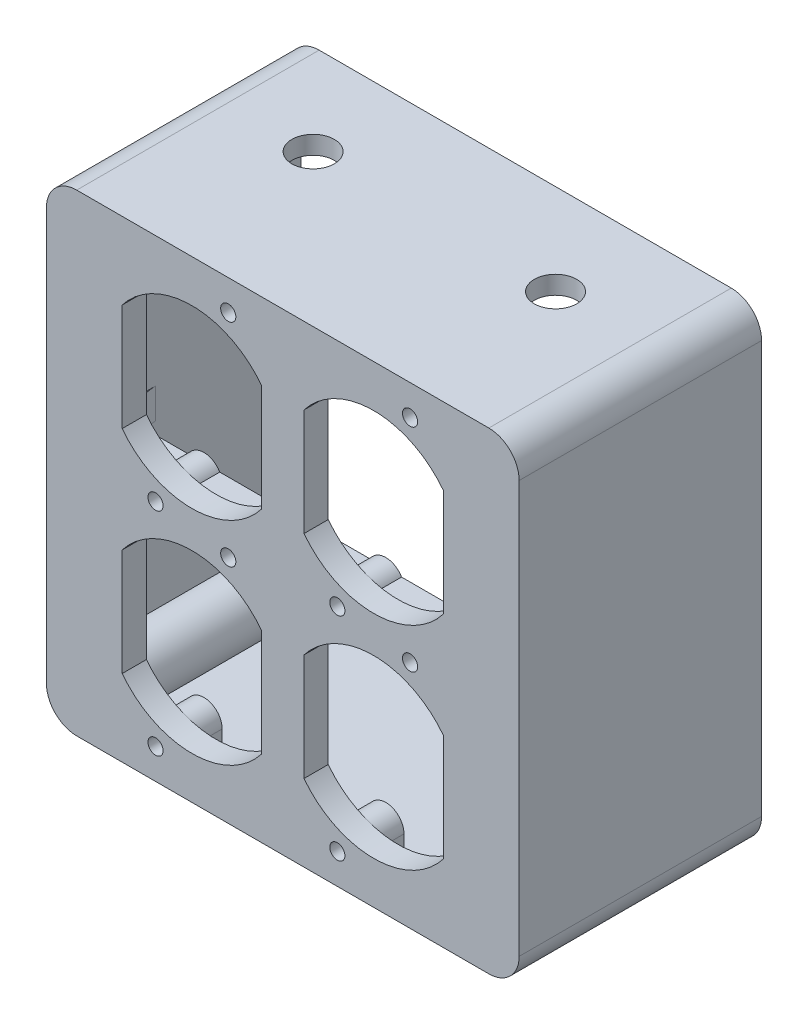
SolidWorks part; units mm, degrees
ref_plane "Front Plane" through (0, 0, 0) normal (0, 0, 1) x (1, 0, 0)
ref_plane "Top Plane" through (0, 0, 0) normal (0, 1, 0) x (1, 0, 0)
ref_plane "Right Plane" through (0, 0, 0) normal (1, 0, 0) x (0, 0, -1)
sketch "Sketch1" plane through (0, 0, 0) normal (0, 0, 1) x (1, 0, 0)
  line L1 (-39, -39) -> (39, -39)
  line L2 (-39, -39) -> (-39, 39)
  line L3 (-39, 39) -> (39, 39)
  line L4 (39, -39) -> (39, 39)
  line L5 (-39, -39) -> (39, 39) construction
  line L6 (-39, 39) -> (39, -39) construction
  point P0 (0, 0)
  dimension "D1" = 78
  dimension "D2" = 78
extrude "Boss-Extrude1" add sketch "Sketch1" along normal blind 40
sketch "Sketch8" plane through (0, 0, 0) normal (0, 0, -1) x (-1, 0, 0)
  line L14 (36, -36) -> (36, 36)
  line L15 (-36, -36) -> (36, -36)
  line L16 (-36, 36) -> (-36, -36)
  line L17 (36, 36) -> (-36, 36)
  line L18 (36, -36) -> (36, 36)
  line L19 (-36, -36) -> (36, -36)
  line L20 (-36, 36) -> (-36, -36)
  line L21 (36, 36) -> (-36, 36)
  dimension "D1" = 3
extrude "Cut-Extrude4" cut sketch "Sketch8" against normal offset from surface (36 mm away) 4 up to face at (0, 0, 40)
sketch "Sketch11" plane through (0, 0, 40) normal (0, 0, 1) x (1, 0, 0)
  line L0 (-39, 39) -> (-39, -39) construction
  line L1 (39, 2.5) -> (-39, 2.5)
  line L2 (39, 2.5) -> (39, -2.5)
  line L3 (39, -2.5) -> (-39, -2.5)
  line L4 (-39, 2.5) -> (-39, -2.5)
  line L5 (39, 2.5) -> (-39, -2.5) construction
  line L6 (39, -2.5) -> (-39, 2.5) construction
  point P0 (0, 0)
  dimension "D1" = 5
extrude "Boss-Extrude4" add sketch "Sketch11" against normal blind 8
sketch "Sketch2" plane through (0, 0, 40) normal (0, 0, 1) x (1, 0, 0)
  line L2 (-26.5, 8.6682) -> (-26.5, 26.3318)
  line L4 (-3.5, 8.6682) -> (-3.5, 26.3318)
  line L5 (-26.5, 8.6682) -> (-3.5, 26.3318) construction
  line L6 (-26.5, 26.3318) -> (-3.5, 8.6682) construction
  arc A0 (-26.5, 26.3318) -> (-3.5, 26.3318) centre (-15, 17.5) cw
  arc A1 (-26.5, 8.6682) -> (-3.5, 8.6682) centre (-15, 17.5) ccw
  point P0 (-15, 17.5)
  point P7 (-15, 3)
  point P9 (-15, 32)
  dimension "D1" = 23
  dimension "D2" = 17.5
  dimension "D3" = 15
  dimension "D4" = 29
extrude "Cut-Extrude1" cut sketch "Sketch2" against normal through all
sketch "Sketch3" plane through (0, 0, 40) normal (0, 0, 1) x (1, 0, 0)
  line L0 (-15, 32) -> (-15, 3) construction
  circle A0 centre (-9, 34) radius 1.25
  circle A1 centre (-21, 1) radius 1.25
  arc A2 (-3.5, 26.3318) -> (-26.5, 26.3318) centre (-15, 17.5) ccw construction
  arc A3 (-26.5, 8.6682) -> (-3.5, 8.6682) centre (-15, 17.5) ccw construction
  point P12 (-15, 17.5)
  dimension "D3" = 2.5
  dimension "D1" = 6
  dimension "D2" = 6
  dimension "D4" = 16.5
  dimension "D5" = 16.5
extrude "Cut-Extrude6" cut sketch "Sketch3" against normal through all
pattern_linear "LPattern1" count 2 spacing 35 along (0, -1, 0) count 2 spacing 30 along (1, 0, 0) of "Cut-Extrude1", "Cut-Extrude6"
sketch "Sketch10" plane through (0, 0, 40) normal (0, 0, 1) x (1, 0, 0)
  line L0 (39, 39) -> (-39, 39) construction
  line L1 (-12, 39) -> (-6, 39)
  line L2 (-12, 39) -> (-12, 34)
  line L3 (-12, 34) -> (-6, 34) construction
  line L4 (-6, 39) -> (-6, 34)
  circle A0 centre (-21, 1) radius 3
  arc A1 (-12, 34) -> (-6, 34) centre (-9, 34) ccw
  circle A2 centre (-9, 34) radius 1.25 construction
  circle A3 centre (-21, 1) radius 1.25 construction
  circle A4 centre (-9, 34) radius 1.25
  circle A5 centre (-21, 1) radius 1.25
  dimension "D1" = 6
  dimension "D2" = 6
extrude "Boss-Extrude3" add sketch "Sketch10" against normal blind 8
pattern_linear "LPattern2" count 2 spacing 30 along (1, 0, 0) of "Boss-Extrude3"
ref_axis "Axis1" through (0, 0, -0.5) along (0, 0, 1)
pattern_circular "CirPattern1" count 2 over 360 about axis through (0, 0, -0.5) along (0, 0, 1) of "LPattern2"
sketch "Sketch12" plane through (-39, 0, 0) normal (-1, 0, 0) x (0, 0, 1)
  line L1 (0, 39) -> (0, -39) construction
  line L2 (40, 39) -> (40, -39) construction
  line L3 (30, 5) -> (40, 5)
  line L4 (40, 5) -> (40, -5)
  line L5 (40, -5) -> (30, -5)
  arc A0 (30, 5) -> (30, -5) centre (30, 0) ccw
  point P4 (0, 0)
  dimension "D1" = 10
  dimension "D2" = 10
fillet "Fillet4" radius 5 4 edges at (39, 39, 20) (39, -39, 20) (-39, 39, 20) (-39, -39, 20)
fillet "Fillet5" radius 7 2 edges at (36, 0, 32) (-36, 0, 32)
sketch "Sketch14" plane through (0, 0, 40) normal (0, 0, 1) x (1, 0, 0)
  circle A0 centre (-34, 34) radius 5
  arc A1 (-34, 39) -> (-39, 34) centre (-34, 34) ccw construction
extrude "Boss-Extrude6" add sketch "Sketch14" against normal up to surface (40 mm away) up to face at (0, 0, 0)
sketch "Sketch15" plane through (0, 0, 0) normal (0, 0, -1) x (-1, 0, 0)
  circle A0 centre (34, 34) radius 1.6
  dimension "D1" = 3.2
extrude "Cut-Extrude7" cut sketch "Sketch15" against normal offset from surface (30 mm away) 10 up to face at (0, 0, 40)
mirror "Mirror3" about plane through (0, 0, 0) normal (1, 0, 0) of "Cut-Extrude7", "Boss-Extrude6"
mirror "Mirror4" about plane through (0, 0, 0) normal (0, 1, 0) of "Mirror3"
sketch "Sketch16" plane through (0, 39, 0) normal (0, 1, 0) x (1, 0, 0)
  line L0 (20, -15) -> (-20, -15) construction
  line L2 (0, -15) -> (0, 0) construction
  line L3 (34, 0) -> (-34, 0) construction
  circle A0 centre (20, -15) radius 3.5
  circle A1 centre (-20, -15) radius 3.5
  dimension "D1" = 7
  dimension "D2" = 40
  dimension "D3" = 15
extrude "Cut-Extrude8" cut sketch "Sketch16" against normal up to next
sketch "Sketch18" plane through (0, 0, 0) normal (0, 0, -1) x (-1, 0, 0)
  line L0 (29.4174, 36) -> (-29.4174, 36) construction
  line L1 (36, -29.4174) -> (36, 29.4174) construction
  line L2 (-29.4174, -36) -> (29.4174, -36) construction
  line L3 (-36, 29.4174) -> (-36, -29.4174) construction
  line L4 (29.4174, 36) -> (-29.4174, 36)
  line L5 (36, -29.4174) -> (36, 29.4174)
  line L6 (-29.4174, -36) -> (29.4174, -36)
  line L7 (-36, 29.4174) -> (-36, -29.4174)
  arc A0 (-36, 29.4174) -> (-29.4174, 36) centre (-34, 34) ccw construction
  arc A1 (29.4174, 36) -> (36, 29.4174) centre (34, 34) ccw construction
  arc A2 (36, -29.4174) -> (29.4174, -36) centre (34, -34) ccw construction
  arc A3 (-29.4174, -36) -> (-36, -29.4174) centre (-34, -34) ccw construction
  arc A4 (-36, 29.4174) -> (-29.4174, 36) centre (-34, 34) ccw
  arc A5 (29.4174, 36) -> (36, 29.4174) centre (34, 34) ccw
  arc A6 (36, -29.4174) -> (29.4174, -36) centre (34, -34) ccw
  arc A7 (-29.4174, -36) -> (-36, -29.4174) centre (-34, -34) ccw
extrude "Cut-Extrude-Thin1" cut sketch "Sketch18" against normal blind 3 thin thin type one direction wall 1
